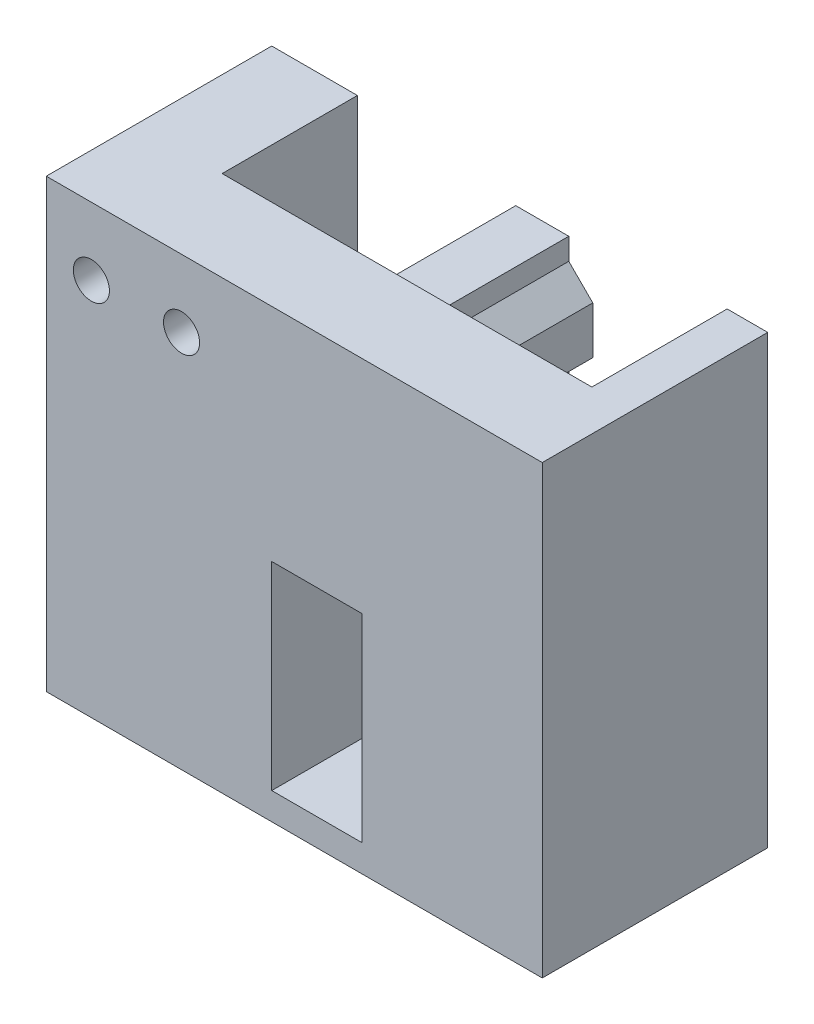
SolidWorks part; units mm, degrees
ref_plane "Front Plane" through (0, 0, 0) normal (0, 0, 1) x (1, 0, 0)
ref_plane "Top Plane" through (0, 0, 0) normal (0, 1, 0) x (1, 0, 0)
ref_plane "Right Plane" through (0, 0, 0) normal (1, 0, 0) x (0, 0, -1)
sketch "Sketch1" plane through (0, 0, 0) normal (0, 0, 1) x (1, 0, 0)
  line L0 (-16.2, -10) -> (-11.5, -10) construction
  line L1 (15, -20) -> (-40, -20)
  line L2 (15, -20) -> (15, 29.5)
  line L4 (-40, -20) -> (-40, 29.5)
  line L6 (10, 8.5) -> (10, 3.8) construction
  line L7 (-30, 28.5) -> (-30, 23.8) construction
  line L8 (-10, -10) -> (-10, 33.7547) construction
  line L9 (-8.5, -10) -> (-11.5, -10) construction
  line L10 (10.5, 10) -> (10.5, 29.5)
  line L11 (10.5, 10) -> (10.5, 3.4944)
  line L12 (10.5, 3.4944) -> (9.7, 2.6)
  line L13 (9.7, 2.6) -> (7.7, 2.6)
  line L14 (7.7, 2.6) -> (7.7, 5)
  line L17 (4.4, 2.6322) -> (4.4, -2.7831)
  line L20 (7.7, -5) -> (7.7, -2.6)
  line L21 (7.7, -2.6) -> (9.7, -2.6)
  line L22 (9.7, -2.6) -> (10.5, -3.4944)
  line L23 (10.5, -3.4944) -> (10.5, -10.5)
  line L24 (10.5, -10.5) -> (-30.5, -10.5)
  line L27 (8.5, -10) -> (3.8, -10) construction
  line L28 (8.2, -3.1) -> (9.3, -3.1) construction
  line L29 (8.2, 3.1) -> (9.3, 3.1) construction
  line L30 (3.9, 2.7565) -> (3.9, -2.7565) construction
  line L31 (8.2, 5.3) -> (8.2, 3.1) construction
  line L32 (8.2, -5.3) -> (8.2, -3.1) construction
  line L33 (10, -3.8) -> (10, -8.5) construction
  line L34 (7.7, -5) -> (6.7678, -5)
  line L35 (6.7678, -5) -> (4.4, -2.7831)
  line L37 (6.5607, -5.5) -> (8, -5.5) construction
  line L38 (4.4, 2.6322) -> (6.7678, 5)
  line L39 (3.9586, 2.8979) -> (6.5607, 5.5) construction
  line L40 (6.7678, 5) -> (7.7, 5)
  line L41 (6.5607, 5.5) -> (8, 5.5) construction
  line L43 (-26.7678, 5) -> (-27.7, 5)
  line L44 (-24.4, 2.6322) -> (-26.7678, 5)
  line L45 (-24.4, 2.6322) -> (-24.4, -2.7831)
  line L46 (-26.7678, -5) -> (-24.4, -2.7831)
  line L47 (-27.7, -5) -> (-26.7678, -5)
  line L48 (-27.7, -5) -> (-27.7, -2.6)
  line L49 (-27.7, -2.6) -> (-29.7, -2.6)
  line L50 (-29.7, -2.6) -> (-30.5, -3.4944)
  line L51 (-30.5, -3.4944) -> (-30.5, -10.5)
  line L52 (-30.5, 10) -> (-30.5, 3.4944)
  line L53 (-30.5, 3.4944) -> (-29.7, 2.6)
  line L54 (-29.7, 2.6) -> (-27.7, 2.6)
  line L55 (-27.7, 2.6) -> (-27.7, 5)
  line L56 (10.5, 29.5) -> (15, 29.5)
  line L58 (-40, 29.5) -> (-30.5, 29.5)
  line L59 (-30.5, 29.5) -> (-30.5, 10)
  dimension "D1" = 10
  dimension "D3" = 5
  dimension "D4" = 10
  dimension "D5" = 0.5
  dimension "D6" = 0.5
  dimension "D7" = 0.5
  dimension "D8" = 0.5
  dimension "D9" = 0.5
  dimension "D10" = 0.5
  dimension "D11" = 0.5
  dimension "D12" = 0.5
  dimension "D14" = 0.5
  dimension "D16" = 0.5
  dimension "D17" = 0.5
  dimension "D19" = 1.2
  dimension "D20" = 1.2
  dimension "D21" = 0.4
  dimension "D22" = 0.4
extrude "Boss-Extrude1" add sketch "Sketch1" against normal blind 15
sketch "Sketch3" plane through (0, 0, 0) normal (0, 0, 1) x (1, 0, 0)
  line L1 (15, -20) -> (-40, -20)
  line L2 (15, -20) -> (15, 29.5)
  line L3 (15, 29.5) -> (-40, 29.5)
  line L4 (-40, -20) -> (-40, 29.5)
extrude "Boss-Extrude2" add sketch "Sketch3" along normal blind 10
sketch "Sketch4" plane through (0, 0, 0) normal (0, 0, -1) x (-1, 0, 0)
  line L0 (12.9393, 25.2929) -> (15.6, 22.6322)
  line L1 (15.6, 22.6322) -> (15.6, 17.3678)
  line L2 (15.6, 17.3678) -> (12.9393, 14.7071)
  line L3 (12.9393, 14.7071) -> (12.9393, 12.3)
  line L4 (12.9393, 12.3) -> (7.0607, 12.3)
  line L5 (7.0607, 12.3) -> (7.0607, 14.7071)
  line L6 (7.0607, 14.7071) -> (4.4, 17.3678)
  line L7 (4.4, 17.3678) -> (4.4, 22.6322)
  line L8 (4.4, 22.6322) -> (7.0607, 25.2929)
  line L9 (7.0607, 25.2929) -> (7.0607, 27.7)
  line L10 (7.0607, 27.7) -> (12.9393, 27.7)
  line L11 (12.9393, 27.7) -> (12.9393, 25.2929)
  line L12 (6.5607, 11.8) -> (13.4393, 11.8) construction
  line L13 (6.5607, 28.2) -> (13.4393, 28.2) construction
  line L14 (3.9586, 22.8979) -> (6.5607, 25.5) construction
  line L15 (16.0414, 17.1021) -> (13.4393, 14.5) construction
  line L16 (13.4393, 14.5) -> (13.4393, 11.8) construction
  line L17 (6.5607, 14.5) -> (6.5607, 11.8) construction
  line L18 (3.9, 22.7565) -> (3.9, 17.2435) construction
  line L19 (16.1, 22.7565) -> (16.1, 17.2435) construction
  line L20 (16.0414, 22.8979) -> (13.4393, 25.5) construction
  line L21 (6.5607, 25.5) -> (6.5607, 28.2) construction
  line L22 (3.9586, 17.1021) -> (6.5607, 14.5) construction
  line L23 (13.4393, 25.5) -> (13.4393, 28.2) construction
  point P14 (10, 27.7)
  dimension "D1" = 0.5
  dimension "D2" = 0.5
  dimension "D3" = 0.5
  dimension "D4" = 0.5
  dimension "D5" = 0.5
  dimension "D6" = 0.5
  dimension "D7" = 0.5
  dimension "D8" = 0.5
  dimension "D9" = 0.5
  dimension "D10" = 0.5
  dimension "D11" = 0.5
  dimension "D13" = 0.5
extrude "Boss-Extrude3" add sketch "Sketch4" along normal blind 15 separate body
sketch "Sketch5" plane through (0, 0, 10) normal (0, 0, 1) x (1, 0, 0)
  line L0 (-40, 29.5) -> (-40, -20) construction
  line L1 (15, 29.5) -> (-40, 29.5) construction
  circle A0 centre (-35, 22) radius 2
  circle A1 centre (-25, 22) radius 2
  dimension "D1" = 4
  dimension "D2" = 4
  dimension "D3" = 5
  dimension "D4" = 7.5
  dimension "D5" = 15
  dimension "D6" = 7.5
extrude "Cut-Extrude1" cut sketch "Sketch5" against normal blind 7
sketch "Sketch6" plane through (0, -20, 0) normal (0, -1, 0) x (-1, 0, 0)
  line L1 (40, -10) -> (-15, -10) construction
  line L2 (40, 15) -> (40, -10) construction
  circle A0 centre (35, -1) radius 2
  circle A1 centre (25, -1) radius 2
  dimension "D1" = 4
  dimension "D2" = 9
  dimension "D3" = 5
  dimension "D4" = 4
  dimension "D5" = 9
  dimension "D6" = 10
extrude "Cut-Extrude2" cut sketch "Sketch6" against normal blind 7
sketch "Sketch7" plane through (0, 0, 10) normal (0, 0, 1) x (1, 0, 0)
  line L0 (-40, -20) -> (15, -20) construction
  line L1 (-15, 5) -> (-5, 5)
  line L2 (-15, 5) -> (-15, -17)
  line L3 (-15, -17) -> (-5, -17)
  line L4 (-5, 5) -> (-5, -17)
  point P4 (-10, -17)
  point P7 (-12.5, -20)
  dimension "D1" = 2.5
  dimension "D2" = 3
  dimension "D3" = 22
  dimension "D4" = 10
extrude "Cut-Extrude3" cut sketch "Sketch7" against normal blind 43
